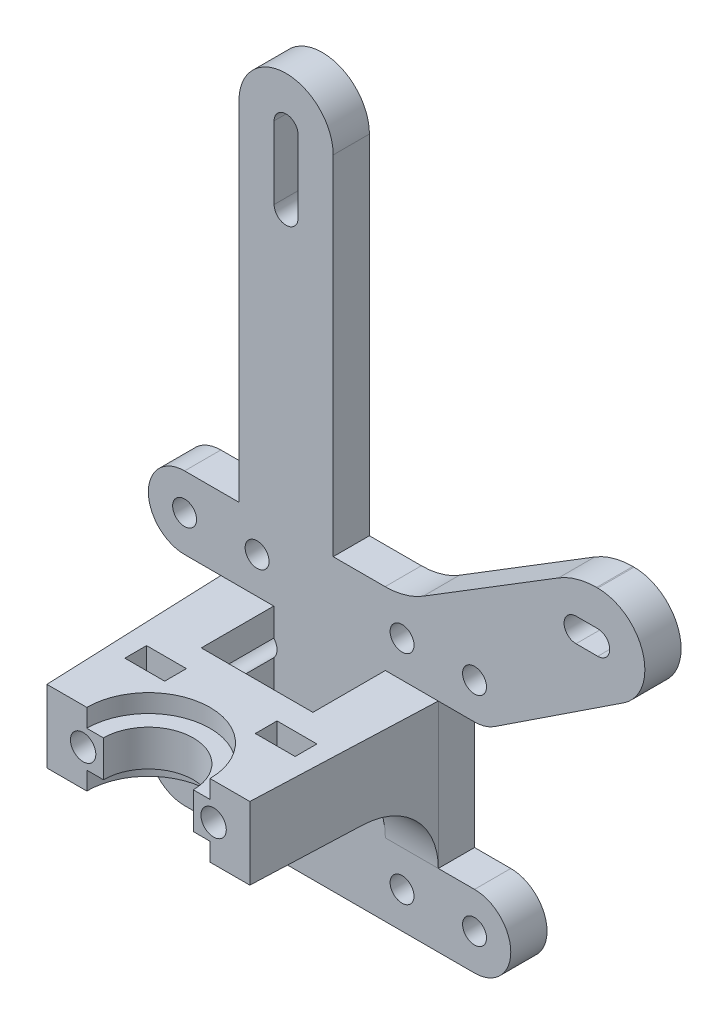
SolidWorks part; units mm, degrees
ref_plane "Plano frontal" through (0, 0, 0) normal (0, 0, 1) x (1, 0, 0)
ref_plane "Plano superior" through (0, 0, 0) normal (0, 1, 0) x (1, 0, 0)
ref_plane "Plano direito" through (0, 0, 0) normal (1, 0, 0) x (0, 0, -1)
sketch "Esboço1" plane through (0, 0, 0) normal (0, 0, 1) x (1, 0, 0)
  line L0 (0.5, 68) -> (0.5, 33.5)
  line L1 (-15, 20) -> (-12.5, 20)
  line L2 (-15, 20) -> (-15, -20)
  line L3 (-15, -20) -> (15, -20)
  line L4 (15, 21.5) -> (15, -20)
  line L5 (-15, 20) -> (15, -20) construction
  line L6 (-15, -20) -> (15, 20) construction
  line L7 (-12.5, 68) -> (-12.5, 20)
  line L8 (15, 20) -> (15, 21.5) construction
  line L9 (-6, 68) -> (-6, 58) construction
  line L10 (-4.35, 68) -> (-4.35, 58)
  line L11 (-7.65, 68) -> (-7.65, 58)
  line L12 (37, 21.5) -> (15, 21.5)
  line L14 (34, 26.35) -> (37, 26.35)
  line L15 (34, 29.65) -> (37, 29.65)
  line L16 (0.5, 33.5) -> (0.5, 20)
  line L17 (0.5, 20) -> (10.5, 20)
  line L18 (37, 34.5) -> (34, 34.5)
  line L19 (34, 34.5) -> (10.5, 20)
  arc A0 (0.5, 68) -> (-12.5, 68) centre (-6, 68) ccw
  arc A1 (-4.35, 68) -> (-7.65, 68) centre (-6, 68) ccw
  arc A2 (-7.65, 58) -> (-4.35, 58) centre (-6, 58) ccw
  arc A3 (37, 21.5) -> (37, 34.5) centre (37, 28) ccw
  arc A4 (37, 26.35) -> (37, 29.65) centre (37, 28) ccw
  arc A5 (34, 29.65) -> (34, 26.35) centre (34, 28) ccw
  point P5 (-6, 63)
  point P6 (0, 0)
  dimension "D3" = 1.65
  dimension "D6" = 6.5
  dimension "D8" = 3.3
  dimension "D1" = 30
  dimension "D2" = 40
  dimension "D4" = 10
  dimension "D5" = 38
  dimension "D7" = 21
  dimension "D9" = 43
  dimension "D10" = 40
  dimension "D11" = 3
  dimension "D12" = 3
  dimension "D13" = 10
extrude "Ressalto-extrusão1" add sketch "Esboço1" along normal blind 5
sketch "Esboço2" plane through (0, 0, 0) normal (0, 1, 0) x (1, 0, 0)
  line L0 (14, -30) -> (15, -5)
  line L1 (-12.5, -5) -> (-15, -5) construction
  line L2 (15, -5) -> (7.7, -5)
  line L3 (-15, -5) -> (-14, -30)
  line L4 (-14, -30) -> (-6.2, -30)
  line L5 (6.2, -30) -> (14, -30)
  line L6 (-7.7, -5) -> (-15, -5)
  line L7 (0, 0) -> (0, -14.0117) construction
  line L8 (-7.7, -5) -> (-7.7, -15)
  line L9 (-7.7, -15) -> (7.7, -15)
  line L10 (7.7, -5) -> (7.7, -15)
  line L11 (-11.75, -18.5) -> (-6.25, -18.5)
  line L12 (-11.75, -18.5) -> (-11.75, -21.5)
  line L13 (-11.75, -21.5) -> (-6.25, -21.5)
  line L14 (-6.25, -18.5) -> (-6.25, -21.5)
  line L15 (-11.75, -18.5) -> (-6.25, -21.5) construction
  line L16 (-11.75, -21.5) -> (-6.25, -18.5) construction
  line L17 (11.75, -21.5) -> (6.25, -18.5) construction
  line L18 (11.75, -18.5) -> (6.25, -21.5) construction
  line L19 (6.25, -18.5) -> (6.25, -21.5)
  line L20 (11.75, -21.5) -> (6.25, -21.5)
  line L21 (11.75, -18.5) -> (11.75, -21.5)
  line L22 (11.75, -18.5) -> (6.25, -18.5)
  arc A0 (6.2, -30) -> (-6.2, -30) centre (0, -30) ccw
  point P10 (-9, -20)
  point P26 (9, -20)
  dimension "D2" = 6.2
  dimension "D1" = 28
  dimension "D3" = 25
  dimension "D4" = 30
  dimension "D5" = 10
  dimension "D6" = 15.4
  dimension "D7" = 5.5
  dimension "D8" = 3
  dimension "D9" = 18
  dimension "D10" = 10
extrude "Ressalto-extrusão2" add sketch "Esboço2" along normal blind 10
sketch "Esboço4" plane through (0, 0, 0) normal (1, 0, 0) x (0, 0, -1)
  line L0 (-30, 10) -> (-21.5, 10)
  line L1 (-30, 10) -> (-5, 10) construction
  line L2 (-21.5, 10) -> (-21.5, 7.5)
  line L3 (-21.5, 7.5) -> (-30, 7.5)
  line L4 (-30, 10) -> (-30, 0) construction
  line L5 (-30, 7.5) -> (-30, 10)
  line L6 (-30, 5) -> (-23.0389, 5) construction
  line L7 (-30, 2.5) -> (-30, 0)
  line L8 (-21.5, 2.5) -> (-30, 2.5)
  line L9 (-21.5, 0) -> (-21.5, 2.5)
  line L10 (-30, 0) -> (-21.5, 0)
  line L11 (-30, 10) -> (-30, -14.7203) construction
  dimension "D1" = 5
  dimension "D2" = 8.5
revolve "Corte-Revolução3" cut sketch "Esboço4" angle 360 about L11
sketch "Esboço6" plane through (0, 0, 30) normal (0, 0, 1) x (1, 0, 0)
  line L0 (0, 0) -> (0, 20.7373) construction
  line L1 (-6.2, 7.5) -> (-6.2, 2.5) construction
  circle A0 centre (-9, 5) radius 1.75
  circle A1 centre (9, 5) radius 1.75
  point P11 (-6.2, 5)
  dimension "D1" = 3.5
  dimension "D2" = 18
extrude "Corte-extrusão2" cut sketch "Esboço6" against normal through all
sketch "Esboço7" plane through (0, 0, 5) normal (0, 0, 1) x (1, 0, 0)
  line L0 (0, 20) -> (0, -20) construction
  line L2 (-15, -20) -> (15, -20) construction
  line L3 (-12.5, 20) -> (-15, 20) construction
  circle A0 centre (-10, 15) radius 1.65
  circle A1 centre (-10, -15) radius 1.65
  circle A2 centre (10, -15) radius 1.65
  circle A3 centre (10, 15) radius 1.65
  dimension "D3" = 3.3
  dimension "D1" = 30
  dimension "D2" = 20
  dimension "D4" = 5
extrude "Corte-extrusão3" cut sketch "Esboço7" against normal blind 10
sketch "Esboço8" plane through (0, 0, 0) normal (0, 0, -1) x (-1, 0, 0)
  line L0 (20, 20) -> (15, 20)
  line L1 (15, 20) -> (15, -20) construction
  line L2 (15, 20) -> (15, 10)
  line L3 (15, 10) -> (20, 10)
  line L4 (0, 0) -> (0, 19.5) construction
  line L5 (-15, 10) -> (-20, 10)
  line L6 (-15, 21.5) -> (-15, 10)
  line L7 (-37, 21.5) -> (-15, 21.5)
  line L9 (0, 0) -> (25, 0) construction
  line L10 (15, -10) -> (20, -10)
  line L11 (15, -20) -> (15, -10)
  line L12 (20, -20) -> (15, -20)
  line L13 (-20, -20) -> (-15, -20)
  line L14 (-15, -20) -> (-15, -10)
  line L15 (-15, -10) -> (-20, -10)
  line L16 (-40.5768, 22.5726) -> (-22.7514, 10.8251)
  arc A0 (-20, 10) -> (-22.7514, 10.8251) centre (-20, 15) cw
  circle A1 centre (20, 15) radius 1.65
  arc A2 (20, 10) -> (20, 20) centre (20, 15) ccw
  circle A3 centre (-20, 15) radius 1.65
  arc A4 (20, -10) -> (20, -20) centre (20, -15) cw
  arc A5 (-37, 34.5) -> (-37, 21.5) centre (-37, 28) ccw construction
  circle A6 centre (20, -15) radius 1.65
  circle A7 centre (-20, -15) radius 1.65
  arc A8 (-20, -10) -> (-20, -20) centre (-20, -15) ccw
  arc A10 (-40.5768, 22.5726) -> (-37, 21.5) centre (-37, 28) ccw
  point P22 (-10, 15)
  dimension "D1" = 10
  dimension "D2" = 3.3
  dimension "D3" = 10
extrude "Ressalto-extrusão3" add sketch "Esboço8" against normal blind 5
fillet "Filete3" radius 10 2 edges at (10.5, 20, 2.5) (34, 34.5, 2.5)
fillet "Filete4" radius 10 2 edges at (-11.35, 0, 5) (11.35, 0, 5)
